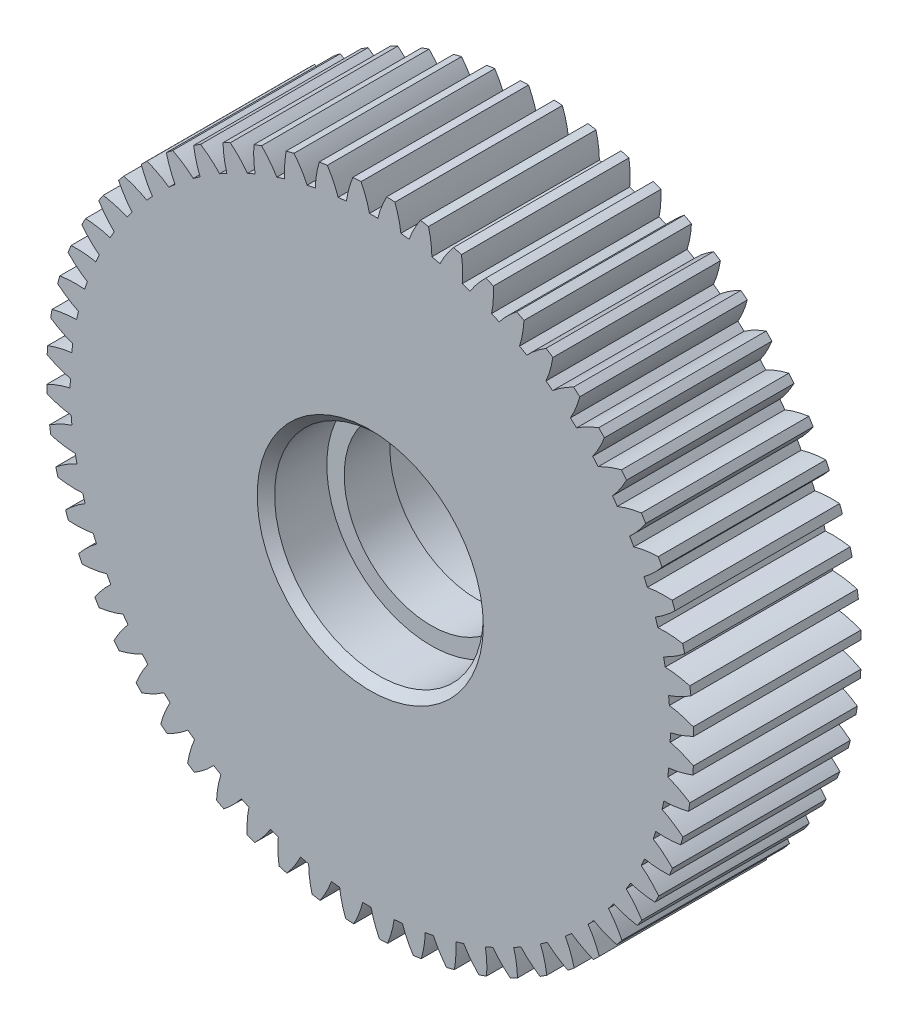
SolidWorks part; units mm, degrees
material "PLA"
ref_plane "Front Plane" through (0, 0, 0) normal (0, 0, 1) x (1, 0, 0)
ref_plane "Top Plane" through (0, 0, 0) normal (0, 1, 0) x (1, 0, 0)
ref_plane "Right Plane" through (0, 0, 0) normal (1, 0, 0) x (0, 0, -1)
sketch "Sketch1" plane through (0, 0, 0) normal (0, 0, 1) x (1, 0, 0)
  circle A0 centre (0, 0) radius 18.6
  dimension "D1" = 37.2
extrude "Boss-Extrude1" add sketch "Sketch1" along normal mid plane 9.6295
sketch "Sketch2" plane through (0, 0, 0) normal (0, 0, 1) x (1, 0, 0)
  line L0 (0, 0) -> (16.9145, 0) construction
  line L1 (0, 0) -> (17.9989, -0.203) construction
  line L2 (0, 0) -> (16.9102, -0.3814) construction
  line L3 (16.9145, 0) -> (17.25, 0)
  line L4 (16.9102, -0.3814) -> (17.2456, -0.389)
  circle A0 centre (0, 0) radius 18 construction
  circle A1 centre (0, 0) radius 16.9145 construction
  circle A2 centre (0, 0) radius 17.25
  circle A3 centre (0, 0) radius 18.6 construction
  circle A4 centre (0, 0) radius 18.6
  spline S0 degree 4 poles (16.9145, 0) (16.9202, 0.0001) (16.9365, 0.0006) (16.9671, 0.0025) (17.017, 0.0071) (17.0805, 0.0151) (17.1623, 0.0279) (17.2585, 0.0461) (17.3637, 0.0693) (17.4778, 0.0981) (17.5911, 0.1299) (17.7037, 0.1645) (17.8154, 0.2015) (17.9501, 0.2494) (18.1107, 0.3111) (18.2971, 0.3893) (18.5068, 0.4851) (18.7185, 0.5904) (18.9251, 0.7002) (19.1317, 0.8182) (19.33, 0.9375) (19.5337, 1.0685) (19.7204, 1.1931) (19.9268, 1.3405) (20.0925, 1.4618) (20.3079, 1.6299) (20.4341, 1.7317) (20.5807, 1.8537) (20.6452, 1.9093) (20.6849, 1.9435) knots 0 0 0 0 0 0.005377 0.015084 0.028532 0.04661 0.064855 0.092111 0.119476 0.146842 0.174209 0.201575 0.228941 0.256307 0.307035 0.361767 0.4165 0.471232 0.525964 0.580697 0.635429 0.690161 0.744894 0.799626 0.854358 0.909091 0.954545 1 1 1 1 1 construction
  spline S1 degree 4 poles (16.9145, 0) (16.9202, 0.0001) (16.9365, 0.0006) (16.9671, 0.0025) (17.017, 0.0071) (17.0805, 0.0151) (17.1623, 0.0279) (17.2585, 0.0461) (17.3637, 0.0693) (17.4778, 0.0981) (17.5911, 0.1299) (17.7037, 0.1645) (17.8154, 0.2015) (17.9501, 0.2494) (18.1107, 0.3111) (18.2971, 0.3893) (18.5068, 0.4851) (18.7185, 0.5904) (18.9251, 0.7002) (19.1317, 0.8182) (19.33, 0.9375) (19.5337, 1.0685) (19.7204, 1.1931) (19.9268, 1.3405) (20.0925, 1.4618) (20.2612, 1.5935) (20.3429, 1.6585) (20.3845, 1.6922) knots 0 0 0 0 0 0.005377 0.015084 0.028532 0.04661 0.064855 0.092111 0.119476 0.146842 0.174209 0.201575 0.228941 0.256307 0.307035 0.361767 0.4165 0.471232 0.525964 0.580697 0.635429 0.690161 0.744894 0.799626 0.854358 0.909091 0.909091 0.909091 0.909091 0.909091
  spline S2 degree 4 poles (16.9102, -0.3814) (16.9159, -0.3816) (16.9321, -0.3825) (16.9627, -0.3851) (17.0125, -0.3909) (17.0758, -0.4003) (17.1573, -0.4149) (17.253, -0.4352) (17.3578, -0.4608) (17.4711, -0.4922) (17.5837, -0.5265) (17.6955, -0.5636) (17.8063, -0.6032) (17.9399, -0.6541) (18.0991, -0.7194) (18.2837, -0.8018) (18.4912, -0.9023) (18.7005, -1.0123) (18.9045, -1.1268) (19.1084, -1.2494) (19.304, -1.3731) (19.5046, -1.5087) (19.6885, -1.6375) (19.8915, -1.7895) (20.0544, -1.9145) (20.2659, -2.0875) (20.3899, -2.1921) (20.5337, -2.3173) (20.5969, -2.3743) (20.6358, -2.4094) knots 0 0 0 0 0 0.005377 0.015084 0.028532 0.04661 0.064855 0.092111 0.119476 0.146842 0.174209 0.201575 0.228941 0.256307 0.307035 0.361767 0.4165 0.471232 0.525964 0.580697 0.635429 0.690161 0.744894 0.799626 0.854358 0.909091 0.954545 1 1 1 1 1 construction
  spline S3 degree 4 poles (16.9102, -0.3814) (16.9159, -0.3816) (16.9321, -0.3825) (16.9627, -0.3851) (17.0125, -0.3909) (17.0758, -0.4003) (17.1573, -0.4149) (17.253, -0.4352) (17.3578, -0.4608) (17.4711, -0.4922) (17.5837, -0.5265) (17.6955, -0.5636) (17.8063, -0.6032) (17.9399, -0.6541) (18.0991, -0.7194) (18.2837, -0.8018) (18.4912, -0.9023) (18.7005, -1.0123) (18.9045, -1.1268) (19.1084, -1.2494) (19.304, -1.3731) (19.5046, -1.5087) (19.6885, -1.6375) (19.8915, -1.7895) (20.0544, -1.9145) (20.2201, -2.0499) (20.3003, -2.1168) (20.3412, -2.1514) knots 0 0 0 0 0 0.005377 0.015084 0.028532 0.04661 0.064855 0.092111 0.119476 0.146842 0.174209 0.201575 0.228941 0.256307 0.307035 0.361767 0.4165 0.471232 0.525964 0.580697 0.635429 0.690161 0.744894 0.799626 0.854358 0.909091 0.909091 0.909091 0.909091 0.909091
  dimension "D1" = 36
  dimension "D2" = 33.8289
  dimension "D3" = 34.5
  dimension "D4" = 0.646
  dimension "D5" = 0.646
extrude "Cut-Extrude1" cut sketch "Sketch2" against normal through all both and the other way through all contours A2 S3 A4 S1 region at (18.0447, -0.2035, 0)
pattern_circular "CirPattern2" count 60 over 360 about axis through (0, 0, -4.8148) along (0, 0, 1) of "Cut-Extrude1"
sketch "Sketch3" plane through (0, 0, 4.8148) normal (0, 0, 1) x (1, 0, 0)
  circle A0 centre (0, 0) radius 5
  dimension "D1" = 10
extrude "Cut-Extrude2" cut sketch "Sketch3" against normal through all both and the other way through all
sketch "Sketch4" plane through (0, 0, 4.8148) normal (0, 0, 1) x (1, 0, 0)
  circle A0 centre (0, 0) radius 6
  dimension "D1" = 12
extrude "Cut-Extrude3" cut sketch "Sketch4" against normal blind 3.5 contours A0
mirror "Mirror2" about plane through (0, 0, 0) normal (0, 0, 1) of "Cut-Extrude3"
chamfer "Chamfer1" distance 0.5 angle 45 2 edges at (6, 0, 4.8148) (6, 0, -4.8148)
equation "\"Ns\" = 48"
equation "\"module\" = 0.6"
equation "\"pressure angle\" = 20.0"
equation "\"h_a\" = 0.6"
equation "\"h_b\" = 0.75"
equation "\"clr_tip_root\" = 0.15000000000000002"
equation "\"dp_s\" = 28.799999999999997"
equation "\"db_s\" = 27.06314747863416"
equation "\"D1@Sketch1\"=\"dp_fs\" + 2*\"h_a\""
equation "\"fw_s_calc\" = 2.359230083666351"
equation "\"D1@Boss-Extrude1\"=\"fw_fs\"-2mm"
equation "\"D1@Sketch2\"=\"dp_fs\""
equation "\"D2@Sketch2\"=\"db_fs\""
equation "\"D3@Sketch2\"=\"dp_fs\"- 2*\"h_b\""
equation "\"alpha_s\" = 0.8539582918412343"
equation "\"D4@Sketch2\"=\"beta_fs\"/2"
equation "\"beta_s\" = 2.0420834163175314"
equation "\"D5@Sketch2\"=\"beta_fs\"/2"
equation "\"D1@CirPattern2\"=\"Ns_fs\""
equation "\"pressure_angle\" = 20.0"
equation "\"h_f\" = 0.75"
equation "\"bearing_ID\" = 65"
equation "\"bearing_OD\" = 85"
equation "\"bearing_height\" = 10"
equation "\"clearance_planet\" = 1.5"
equation "\"case_dist\" = 6.5"
equation "\"Motor_case_OD_max\" = 115.5"
equation "\"case_mounting_PCD\" = 108.0"
equation "\"bearing mount thickness\" = 8"
equation "\"case_mounting_hole_dia\" = 3"
equation "\"output_mounting_PCD\" = 93"
equation "\"output_mounting_hole_dia\" = 4"
equation "\"clearance_case_mount_holes_shell_thickness\" = 1"
equation "\"motor_case_OD_base\" = 106.0"
equation "\"sec_carrier_thickness\" = 5"
equation "\"sun_coupler_hub_thickness\" = 4"
equation "\"clearance_sun_coupler_sec_carrier\" = 1.5"
equation "\"clearance_motor_and_case\" = 14.5"
equation "\"motor_OD\" = 72"
equation "\"Motor_case_thickness\" = 2.5"
equation "\"Motor_case_ID\" = 101.0"
equation "\"case_mounting_hole_shift\" = 1.0"
equation "\"output_mounting_nut_wrench_size\" = 7"
equation "\"output_mounting_nut_thickness\" = 3.2"
equation "\"case_mounting_hole_allen_socket_dia\" = 5.5"
equation "\"output_mounting_nut_depth\" = 3"
equation "\"case_mounting_bolt_depth\" = 4.5"
equation "\"ring_radial_thickness\" = 5"
equation "\"ring_to_chamfer_clearance\" = 1.5"
equation "\"Motor_case_OD_base_to_chamfer\" = 5"
equation "\"pattern_offset_from_motor_case_OD_base\" = 3"
equation "\"pattern_bulge_dia\" = 3"
equation "\"pattern_num_bulge\" = 18"
equation "\"pattern_depth\" = 2"
equation "\"motor_height\" = 27"
equation "\"case_mounting_wrench_size\" = 5.5"
equation "\"case_mounting_nut_clearance\" = 2"
equation "\"base_plate_thickness\" = 4"
equation "\"case_mounting_nut_thickness\" = 2.4"
equation "\"case_mounting_surface_height\" = 4"
equation "\"motor_mount_hole_PCD\" = 32"
equation "\"motor_mount_hole_dia\" = 4"
equation "\"motor_mount_hole_num\" = 4"
equation "\"central_hole_offset_from_motor_mount_PCD\" = 5"
equation "\"wire_slot_dist_from_center\" = 26"
equation "\"wire_slot_length\" = 10"
equation "\"wire_slot_radius\" = 2.5"
equation "\"driver_upper_holes_dist_from_center\" = 29"
equation "\"driver_lower_holes_dist_from_center\" = 13"
equation "\"driver_side_holes_dist_from_center\" = 22.5"
equation "\"driver_mount_holes_dia\" = 3"
equation "\"driver_mount_inserts_OD\" = 4.8"
equation "\"driver_mount_thickness\" = 1.5"
equation "\"driver_mount_height\" = 6"
equation "\"air_flow_hole_offset\" = 3"
equation "\"num_planet\" = 4"
equation "\"planet_pin_bolt_dia\" = 5"
equation "\"planet_pin_socket_head_dia\" = 8.5"
equation "\"carrier_PCD\" = 52.8"
equation "\"planet_shaft_dia\" = 8"
equation "\"planet_shaft_step_offset\" = 1"
equation "\"carrier_trapezoidal_support_sun_offset\" = 5"
equation "\"carrier_trapezoidal_support_hole_PCD_offset_bearing_ID\" = 4"
equation "\"carrier_trapezoidal_support_hole_dia\" = 3"
equation "\"carrier_trapezoidal_support_hole_socket_head_dia\" = 5.5"
equation "\"carrier_bearing_step_width\" = 1.5"
equation "\"standard_clearance_1_5mm\" = 1.5"
equation "\"standard_fillet_1_5mm\" = 1.5"
equation "\"sun_shaft_bearing_OD\" = 16"
equation "\"sun_shaft_bearing_width\" = 5"
equation "\"standard_bearing_insertion_chamfer\" = 0.5"
equation "\"carrier_trapezoidal_support_hole_wrench_size\" = 5.5"
equation "\"planet_pin_bolt_wrench_size\" = 8"
equation "\"planet_bearing_OD\" = 12"
equation "\"planet_bearing_width\" = 3.5"
equation "\"planet_bore\" = 10"
equation "\"motor_output_hole_PCD\" = 22"
equation "\"motor_output_hole_dia\" = 3"
equation "\"motor_output_hole_num\" = 4"
equation "\"sun_shaft_bearing_ID\" = 8"
equation "\"sun_hub_dia\" = 28.0"
equation "\"sun_central_bolt_dia\" = 5"
equation "\"sun_central_bolt_socket_head_dia\" = 8.5"
equation "\"fw_s_used\" = 31.575468444261382"
equation "\"motor_output_hole_CSK_OD\" = 6"
equation "\"motor_output_hole_CSK_head_height\" = 1.5"
equation "\"Np_b\" = 40"
equation "\"dp_p_b\" = 24.0"
equation "\"db_p_b\" = 22.552622898861802"
equation "\"fw_p_s\" = 11.6295029769434"
equation "\"alpha_p_b\" = 0.8539582918412414"
equation "\"beta_p_b\" = 2.792083416317517"
equation "\"bearing_retainer_thickness\" = 2"
equation "\"Np_s\" = 28"
equation "\"fw_p_b\" = 12.445965467317981"
equation "\"dp_p_s\" = 16.8"
equation "\"db_p_s\" = 15.786836029203263"
equation "\"alpha_p_s\" = 0.8539582918412343"
equation "\"beta_p_s\" = 4.72065484488896"
equation "\"Cut-Extrude9\"= IIF ( ( \"Ns\" * \"module\" + 2 * \"h_a\" ) < ( \"motor_output_hole_PCD\" - \"motor_output_hole_CSK_OD\" ) , \"suppressed\" , \"unsuppressed\" )"
equation "\"Nr_b\" = 128"
equation "\"dp_r_b\" = 76.8"
equation "\"db_r_b\" = 72.16839327635776"
equation "\"fw_r_b\" = 12.445965467317981"
equation "\"alpha_r_b\" = 0.8539582918412556"
equation "\"beta_r_b\" = 3.114166583682511"
equation "\"ring_OD_b\" = 86.8"
equation "\"Fillet10\"= IIF ( \"ring_OD_b\" > ( \"bearing_OD\" + 2 * \"bearing mount thickness\" ) , \"suppressed\" , \"unsuppressed\" )"
equation "\"Fillet11\"= IIF ( \"ring_OD_b\" < ( \"bearing_OD\" + 2 * \"bearing mount thickness\" ) , \"suppressed\" , \"unsuppressed\" )"
equation "\"Nr_s\" = 116"
equation "\"clr_tip_root_s\" = 0.15000000000000002"
equation "\"dp_r_s\" = 69.6"
equation "\"db_r_s\" = 65.40260640669922"
equation "\"fw_r_s\" = 10.1295029769434"
equation "\"alpha_r_s\" = 0.8539582918412343"
equation "\"beta_r_s\" = 3.2596407216135033"
equation "\"small_ring_case_thickness\" = 4"
equation "\"carrier_thickness\" = 4"
equation "\"small_ring_output_wall_thickness\" = 5"
equation "\"small_ring_output_wall_to_bearing_shaft_attachement_hole_dia\" = 4"
equation "\"small_ring_output_wall_to_bearing_shaft_attachement_hole_depth\" = 6.5"
equation "\"small_ring_output_wall_to_bearing_shaft_attachement_nut_wrench\" = 7"
equation "\"small_ring_output_wall_to_bearing_shaft_attachement_nut_thickness\" = 3.2"
equation "\"small_ring_output_wall_to_bearing_shaft_attachement_hole_pcd\" = 12"
equation "\"small_ring_output_wall_to_bearing_shaft_attachement_hole_num\" = 3"
equation "\"small_ring_output_wall_to_bearing_shaft_attachement_hole_CSK_OD\" = 8"
equation "\"small_ring_output_wall_to_bearing_shaft_attachement_hole_CSK_head_height\" = 2.0"
equation "\"carrier_small_ring_inner_bearing_ID\" = 20"
equation "\"carrier_small_ring_inner_bearing_OD\" = 32"
equation "\"carrier_small_ring_inner_bearing_height\" = 7"
equation "\"carrier_small_ring_inner_bearing_flap\" = 2"
equation "\"gear_casing_big_ring_to_bearing_dist\" = 20.6295029769434"
equation "\"gear_casing_thickness\" = 4"
equation "\"tight_clearance_3DP\" = 0.4"
equation "\"loose_clearance_3DP\" = 0.8"
equation "\"Cut-Extrude10\"= IIF ( ( \"Ns\" * \"module\" - 2 * \"h_a\" ) < ( \"motor_output_hole_PCD\" + \"motor_output_hole_dia\" + \"standard_clearance_1_5mm\" * 4 / 3 ) , \"suppressed\" , \"unsuppressed\" )"
equation "\"Ns_fs\" = 60"
equation "\"dp_fs\" = 36.0"
equation "\"db_fs\" = 33.828934348292705"
equation "\"alpha_fs\" = 0.8539582918412343"
equation "\"beta_fs\" = 1.2920834163175314"
equation "\"fw_fs\" = 11.6295029769434"
equation "\"num_idler\" = 4"
equation "\"idler_angle_offset\" = 45.0"
equation "\"fs_bore_dia\"= 31.599999999999998"
equation "\"fs_bore_wall\"= 2.6500000000000004"
equation "\"fs_axial_clearance\"= 0.8"
equation "\"D1@Sketch3\"=\"planet_bore\""
equation "\"D1@Sketch4\"=\"planet_bearing_OD\""
equation "\"D1@Cut-Extrude3\"=\"planet_bearing_width\""
equation "\"D1@Chamfer1\"=\"standard_bearing_insertion_chamfer\""
